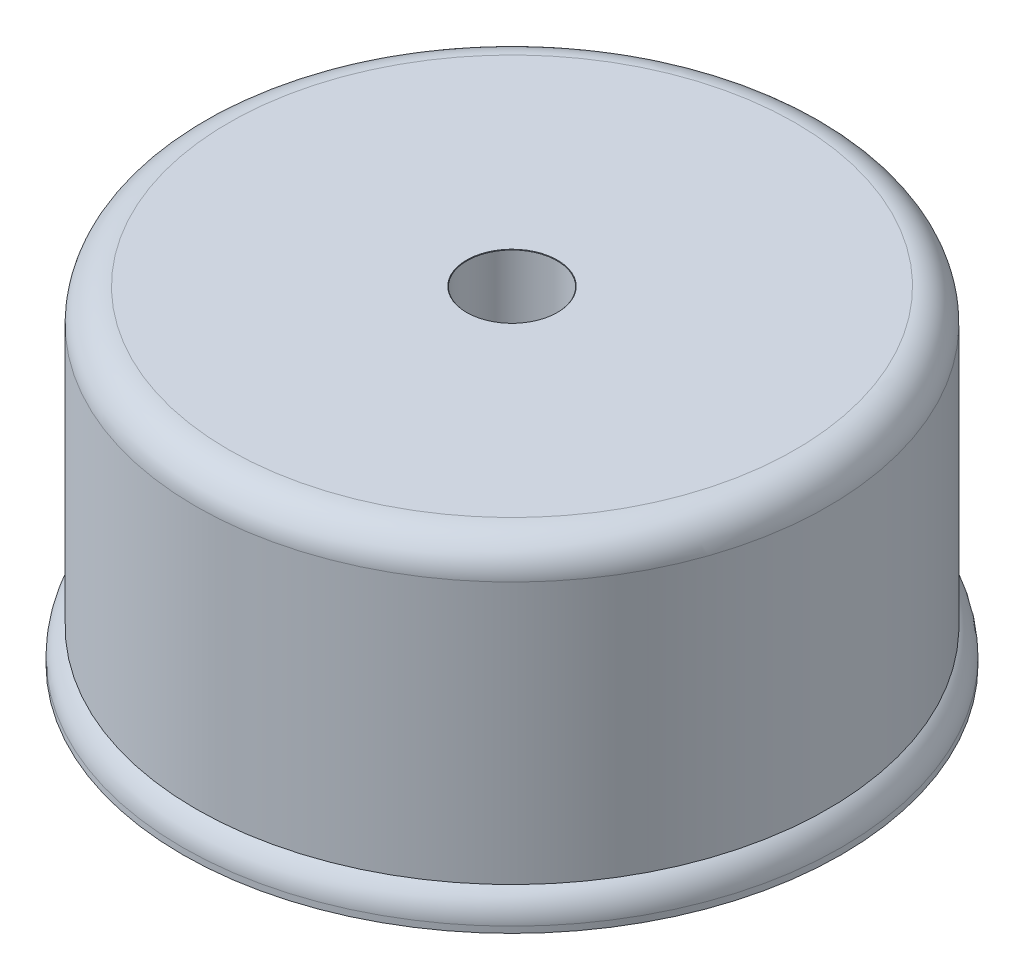
SolidWorks part; units mm, degrees
ref_plane "Front Plane" through (0, 0, 0) normal (0, 0, 1) x (1, 0, 0)
ref_plane "Top Plane" through (0, 0, 0) normal (0, 1, 0) x (1, 0, 0)
ref_plane "Right Plane" through (0, 0, 0) normal (1, 0, 0) x (0, 0, -1)
sketch "Sketch1" plane through (0, 0, 0) normal (0, 1, 0) x (1, 0, 0)
  line L5 (-10.6773, -10.6773) -> (10.6773, 10.6773) construction
  line L6 (-10.6773, 10.6773) -> (10.6773, -10.6773) construction
  circle A0 centre (0, 0) radius 20.125
  dimension "D1" = 40.25
extrude "Boss-Extrude1" add sketch "Sketch1" along normal blind 20
ref_plane "Plane1" through (0, 0, 19.3) normal (0, 0, 1) x (1, 0, 0)
sketch "Sketch12" plane through (0, 0, 0) normal (0, -1, 0) x (1, 0, 0)
  line L1 (-10.748, -10.748) -> (10.748, -10.748)
  line L2 (-10.748, -10.748) -> (-10.748, 10.748)
  line L3 (-10.748, 10.748) -> (10.748, 10.748)
  line L4 (10.748, -10.748) -> (10.748, 10.748)
  line L5 (-10.748, -10.748) -> (10.748, 10.748) construction
  line L6 (-10.748, 10.748) -> (10.748, -10.748) construction
  circle A0 centre (0, 0) radius 15.2 construction
  dimension "D1" = 30.4
extrude "Cut-Extrude1" cut sketch "Sketch12" against normal offset from surface (15 mm away) 15 contours L1 L4 L3 L2 | L2 L1 L4 L3 region at (0, 0, 0) up to face at (0, 0, 20.125)
sketch "Sketch16" plane through (0, 20, 0) normal (0, 1, 0) x (1, 0, 0)
  circle A0 centre (0, 0) radius 19.3
  circle A1 centre (0, 0) radius 20.125
  circle A2 centre (0, 0) radius 20.125 construction
  circle M2 centre (0, 0) radius 20.125
  dimension "D1" = 38.6
extrude "Cut-Extrude2" cut sketch "Sketch16" against normal offset from surface (18 mm away) 2 contours A0 M2 region at (-19.5558, 20, 0) up to face at (0, 0, 0)
fillet "Fillet3" radius 2 2 edges at (0, 20, 19.3) (0, 2, 20.125)
hole_wizard "M5 Clearance Hole1" positions "Sketch23" profile "Sketch24" hole size "M5" standard "ANSI Metric" end condition through all
sketch "Sketch23" plane through (0, 20, 0) normal (0, 1, 0) x (1, 0, 0)
  point P0 (0, 0)
sketch "Sketch24" plane through (0, 20, 0) normal (1, 0, 0) x (0, 0, 1)
  line L0 (0, 0) -> (0, 20)
  line L1 (0, 20) -> (2.75, 20)
  line L2 (2.75, 20) -> (2.75, 0.025)
  line L3 (2.75, 0.025) -> (2.775, 0)
  line L5 (2.775, 0) -> (0, 0)
  line L6 (-2.75, 0.025) -> (-2.775, 0) construction
  line L11 (0, -6.35) -> (0, 107.95) construction
  dimension "Thru Hole Dia." = 5.5
  dimension "Thru Hole Depth" = 20
  dimension "Near C'Sink Dia." = 5.55
  dimension "Near C'Sink Angle" = 90
